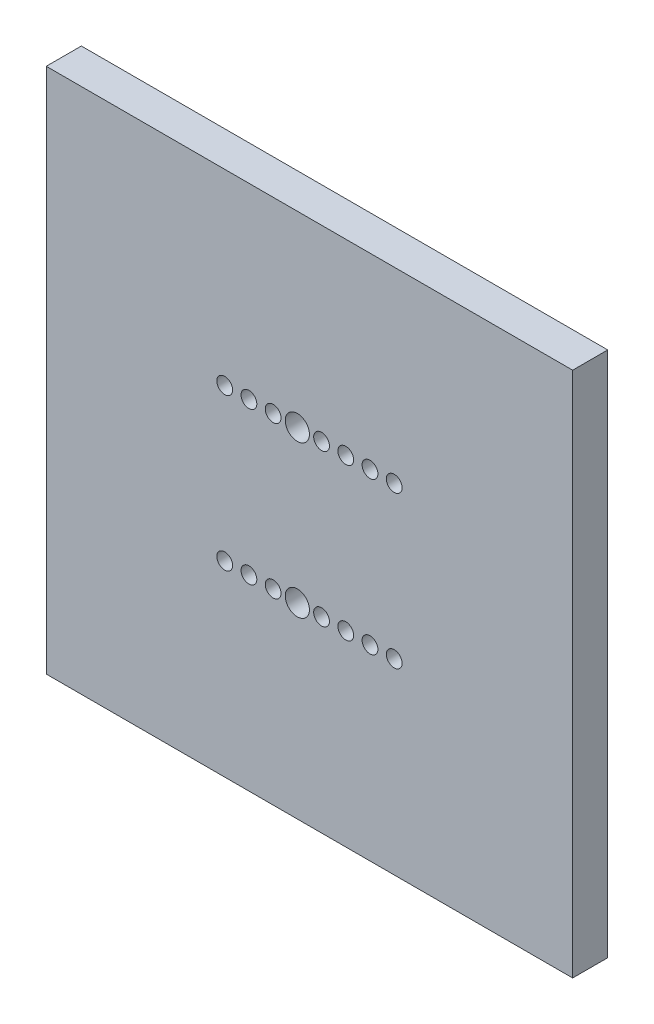
SolidWorks part; units mm, degrees
ref_plane "Plan de face" through (0, 0, 0) normal (0, 0, 1) x (1, 0, 0)
ref_plane "Plan de dessus" through (0, 0, 0) normal (0, 1, 0) x (1, 0, 0)
ref_plane "Plan de droite" through (0, 0, 0) normal (1, 0, 0) x (0, 0, -1)
sketch "Esquisse2" plane through (0, 0, 0) normal (0, 0, 1) x (1, 0, 0)
  line L1 (-15, -15) -> (15, -15)
  line L2 (-15, -15) -> (-15, 15)
  line L3 (-15, 15) -> (15, 15)
  line L4 (15, -15) -> (15, 15)
  line L5 (-15, -15) -> (15, 15) construction
  line L6 (-15, 15) -> (15, -15) construction
  point P0 (0, 0)
extrude "Boss.-Extru.1" add sketch "Esquisse2" along normal blind 2
sketch "Esquisse3" plane through (0, 0, 2) normal (0, 0, 1) x (1, 0, 0)
  circle A0 centre (-4.83, -4.33) radius 0.45
  circle A1 centre (-4.83, 4.33) radius 0.45
  circle A2 centre (-3.45, -4.33) radius 0.45
  circle A3 centre (-3.45, 4.33) radius 0.45
  circle A4 centre (-2.07, -4.33) radius 0.45
  circle A5 centre (-2.07, 4.33) radius 0.45
  circle A6 centre (-0.69, -4.33) radius 0.69
  circle A7 centre (-0.69, 4.33) radius 0.69
  circle A8 centre (0.69, -4.33) radius 0.45
  circle A9 centre (0.69, 4.33) radius 0.45
  circle A10 centre (2.07, -4.33) radius 0.45
  circle A11 centre (2.07, 4.33) radius 0.45
  circle A12 centre (3.45, -4.33) radius 0.45
  circle A13 centre (3.45, 4.33) radius 0.45
  circle A14 centre (4.83, -4.33) radius 0.45
  circle A15 centre (4.83, 4.33) radius 0.45
extrude "Enlèv. mat.-Extru.1" cut sketch "Esquisse3" against normal blind 10
